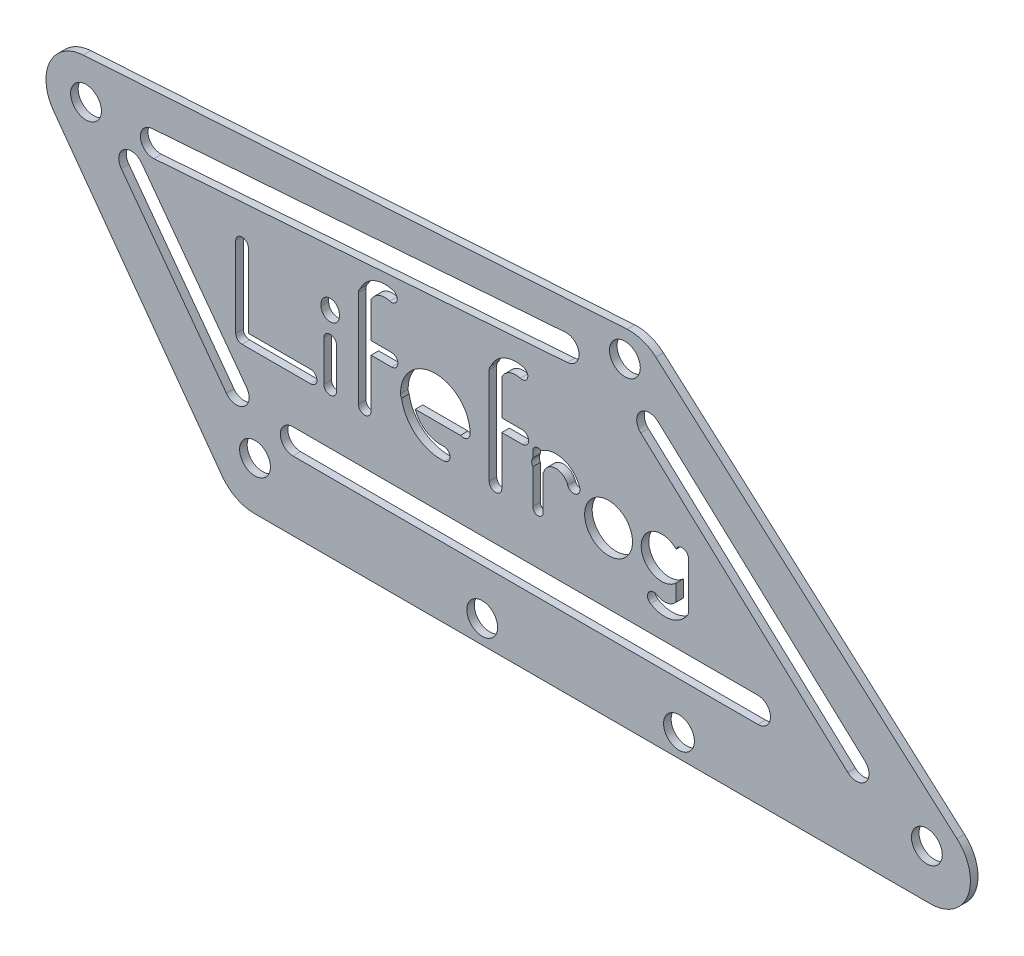
SolidWorks part; units mm, degrees
ref_plane "Front Plane" through (0, 0, 0) normal (0, 0, 1) x (1, 0, 0)
ref_plane "Top Plane" through (0, 0, 0) normal (0, 1, 0) x (1, 0, 0)
ref_plane "Right Plane" through (0, 0, 0) normal (1, 0, 0) x (0, 0, -1)
sketch "Sketch3" plane through (0, 0, 0) normal (0, 0, 1) x (1, 0, 0)
  line L0 (-105.0544, 1.9987) -> (28.8099, 1.9987)
  line L3 (-144.7818, 51.1553) -> (-111.4337, 5.2494)
  line L4 (-130.8953, -6.016) -> (39.056, -6.016)
  line L7 (-138.9015, 63.6585) -> (-31.2776, 70.4842)
  line L8 (-25.5532, 68.52) -> (34.0353, 15.7884)
  arc A0 (28.8099, 1.9987) -> (34.0353, 15.7884) centre (28.8099, 9.8836) ccw
  arc A1 (-25.5532, 68.52) -> (-31.2776, 70.4842) centre (-30.7786, 62.6152) ccw
  arc A2 (-105.0544, 1.9987) -> (-111.4337, 5.2494) centre (-105.0544, 9.8836) cw
  arc A3 (-144.7818, 51.1553) -> (-138.9015, 63.6585) centre (-138.4025, 55.7894) cw
  circle A11 centre (49.307, 58.8735) radius 21
  circle A13 centre (-59.9429, 6.5523) radius 3.05
  circle A14 centre (-104.9148, 11.5444) radius 3.05
  circle A15 centre (-20.9941, 6.4971) radius 3.05
  circle A16 centre (28.0724, 11.5486) radius 3.05
  circle A17 centre (-31.7004, 65.1519) radius 3.05
  circle A18 centre (-138.3619, 55.8478) radius 3.05
  dimension "D1" = 7.8849
  dimension "D2" = 6.1
extrude "Boss-Extrude2" add sketch "Sketch3" along normal blind 1.5 contours A3 L3 A2 L0 A0 L8 A1 L7 A18 A17 A16 A15 A14 A13 region at (-58.2224, 33.7177, 0)
sketch "Sketch4" plane through (0, 0, 1.5) normal (0, 0, 1) x (1, 0, 0)
  line L1 (-26.8632, 55.8937) -> (14.1152, 18.1826) construction
  line L5 (-25.1703, 57.7333) -> (15.8082, 20.0221)
  line L9 (-28.5561, 54.0541) -> (12.4223, 16.343)
  line L13 (-97.4073, 18.1826) -> (-5.3775, 18.1826) construction
  line L23 (-129.3887, 49.4647) -> (-108.5686, 21.3307) construction
  line L26 (-127.3791, 50.9519) -> (-106.559, 22.8178)
  line L29 (-131.3983, 47.9776) -> (-110.5782, 19.8435)
  line L30 (-125.1067, 55.383) -> (-43.278, 61.3603) construction
  line L31 (-125.2888, 57.8764) -> (-43.4601, 63.8537)
  line L32 (-124.9246, 52.8897) -> (-43.0958, 58.867)
  line L33 (-97.4073, 20.6826) -> (-5.3775, 20.6826)
  line L34 (-97.4073, 15.6826) -> (-5.3775, 15.6826)
  line L35 (-107.4816, 46.9298) -> (-107.4816, 31.0422) construction
  line L36 (-106.2316, 46.9298) -> (-106.2316, 31.0422)
  line L37 (-108.7316, 46.9298) -> (-108.7316, 31.0422)
  line L38 (-107.4816, 31.0422) -> (-93.9009, 31.0422) construction
  line L39 (-107.4816, 32.2922) -> (-93.9009, 32.2922)
  line L40 (-107.4816, 29.7922) -> (-93.9009, 29.7922)
  line L41 (-90.0274, 38.986) -> (-90.0274, 31.0422) construction
  line L42 (-88.7774, 38.986) -> (-88.7774, 31.0422)
  line L43 (-91.2774, 38.986) -> (-91.2774, 31.0422)
  line L44 (-90.0274, 44.5942) -> (-90.0274, 44.1452) construction
  line L45 (-88.2261, 44.5942) -> (-88.2261, 44.1452)
  line L46 (-91.8287, 44.5942) -> (-91.8287, 44.1452)
  line L47 (-83.1958, 31.0422) -> (-83.1958, 50.1599) construction
  line L48 (-84.4458, 31.0422) -> (-84.4458, 50.1599)
  line L49 (-81.9458, 31.0422) -> (-81.9458, 50.1599)
  line L50 (-83.1958, 41.9365) -> (-77.886, 41.9365) construction
  line L51 (-83.1958, 43.1865) -> (-77.886, 43.1865)
  line L52 (-83.1958, 40.6865) -> (-77.886, 40.6865)
  line L53 (-74.7394, 37.0381) -> (-63.7024, 37.0381) construction
  line L54 (-74.7394, 38.2881) -> (-63.7024, 38.2881)
  line L55 (-74.7394, 35.7881) -> (-63.7024, 35.7881)
  line L56 (-57.316, 30.7325) -> (-57.316, 49.8502) construction
  line L57 (-58.566, 30.7325) -> (-58.566, 49.8502)
  line L58 (-56.066, 30.7325) -> (-56.066, 49.8502)
  line L59 (-57.316, 41.6268) -> (-52.0062, 41.6268) construction
  line L60 (-57.316, 42.8768) -> (-52.0062, 42.8768)
  line L61 (-57.316, 40.3768) -> (-52.0062, 40.3768)
  line L62 (-48.9003, 30.7325) -> (-48.9003, 40.2914) construction
  line L63 (-49.9346, 30.7325) -> (-49.9346, 40.2914)
  line L64 (-47.8659, 30.7325) -> (-47.8659, 40.2914)
  line L65 (-20.3592, 37.2289) -> (-20.3592, 28.1084) construction
  line L66 (-19.1092, 37.2289) -> (-19.1092, 28.1084)
  line L67 (-21.6092, 37.2289) -> (-21.6092, 28.1084)
  arc A16 (-127.3791, 50.9519) -> (-131.3983, 47.9776) centre (-129.3887, 49.4647) ccw
  arc A17 (-110.5782, 19.8435) -> (-106.559, 22.8178) centre (-108.5686, 21.3307) ccw
  arc A18 (-125.2888, 57.8764) -> (-124.9246, 52.8897) centre (-125.1067, 55.383) ccw
  arc A19 (-43.0958, 58.867) -> (-43.4601, 63.8537) centre (-43.278, 61.3603) ccw
  arc A20 (-25.1703, 57.7333) -> (-28.5561, 54.0541) centre (-26.8632, 55.8937) ccw
  arc A21 (12.4223, 16.343) -> (15.8082, 20.0221) centre (14.1152, 18.1826) ccw
  arc A22 (-97.4073, 20.6826) -> (-97.4073, 15.6826) centre (-97.4073, 18.1826) ccw
  arc A23 (-5.3775, 15.6826) -> (-5.3775, 20.6826) centre (-5.3775, 18.1826) ccw
  arc A24 (-106.2316, 46.9298) -> (-108.7316, 46.9298) centre (-107.4816, 46.9298) ccw
  arc A25 (-108.7316, 31.0422) -> (-106.2316, 31.0422) centre (-107.4816, 31.0422) ccw
  arc A26 (-107.4816, 32.2922) -> (-107.4816, 29.7922) centre (-107.4816, 31.0422) ccw
  arc A27 (-93.9009, 29.7922) -> (-93.9009, 32.2922) centre (-93.9009, 31.0422) ccw
  arc A28 (-88.7774, 38.986) -> (-91.2774, 38.986) centre (-90.0274, 38.986) ccw
  arc A29 (-91.2774, 31.0422) -> (-88.7774, 31.0422) centre (-90.0274, 31.0422) ccw
  arc A30 (-88.2261, 44.5942) -> (-91.8287, 44.5942) centre (-90.0274, 44.5942) ccw
  arc A31 (-91.8287, 44.1452) -> (-88.2261, 44.1452) centre (-90.0274, 44.1452) ccw
  arc A32 (-84.4458, 31.0422) -> (-81.9458, 31.0422) centre (-83.1958, 31.0422) ccw
  arc A33 (-81.9458, 50.1599) -> (-84.4458, 50.1599) centre (-83.1958, 50.1599) ccw
  arc A34 (-83.1958, 50.1599) -> (-77.886, 52.8897) centre (-79.176, 48.8699) cw construction
  arc A35 (-77.5399, 53.9683) -> (-84.2744, 50.5061) centre (-79.176, 48.8699) ccw
  arc A36 (-78.2322, 51.8111) -> (-82.1172, 49.8138) centre (-79.176, 48.8699) ccw
  arc A37 (-78.2322, 51.8111) -> (-77.5399, 53.9683) centre (-77.886, 52.8897) ccw
  arc A38 (-84.2744, 50.5061) -> (-82.1172, 49.8138) centre (-83.1958, 50.1599) ccw
  arc A39 (-83.1958, 43.1865) -> (-83.1958, 40.6865) centre (-83.1958, 41.9365) ccw
  arc A40 (-77.886, 40.6865) -> (-77.886, 43.1865) centre (-77.886, 41.9365) ccw
  arc A41 (-74.7394, 38.2881) -> (-74.7394, 35.7881) centre (-74.7394, 37.0381) ccw
  arc A42 (-63.7024, 35.7881) -> (-63.7024, 38.2881) centre (-63.7024, 37.0381) ccw
  arc A43 (-74.7394, 37.0381) -> (-63.7024, 37.0381) centre (-69.2209, 37.0381) cw construction
  arc A44 (-62.3325, 37.0381) -> (-76.1093, 37.0381) centre (-69.2209, 37.0381) ccw
  arc A45 (-65.0723, 37.0381) -> (-73.3696, 37.0381) centre (-69.2209, 37.0381) ccw
  arc A46 (-65.0723, 37.0381) -> (-62.3325, 37.0381) centre (-63.7024, 37.0381) ccw
  arc A47 (-76.1093, 37.0381) -> (-73.3696, 37.0381) centre (-74.7394, 37.0381) ccw
  arc A48 (-74.7394, 37.0381) -> (-67.5709, 31.0113) centre (-68.1417, 37.609) ccw construction
  arc A49 (-75.9848, 36.9304) -> (-67.4631, 29.766) centre (-68.1417, 37.609) ccw
  arc A50 (-73.4941, 37.1459) -> (-67.6786, 32.2567) centre (-68.1417, 37.609) ccw
  arc A51 (-73.4941, 37.1459) -> (-75.9848, 36.9304) centre (-74.7394, 37.0381) ccw
  arc A52 (-67.4631, 29.766) -> (-67.6786, 32.2567) centre (-67.5709, 31.0113) ccw
  arc A53 (-58.566, 30.7325) -> (-56.066, 30.7325) centre (-57.316, 30.7325) ccw
  arc A54 (-56.066, 49.8502) -> (-58.566, 49.8502) centre (-57.316, 49.8502) ccw
  arc A55 (-57.316, 49.8502) -> (-52.0438, 52.5918) centre (-53.2963, 48.5602) cw construction
  arc A56 (-51.7077, 53.6736) -> (-58.3946, 50.1964) centre (-53.2963, 48.5602) ccw
  arc A57 (-52.3798, 51.5101) -> (-56.2374, 49.5041) centre (-53.2963, 48.5602) ccw
  arc A58 (-52.3798, 51.5101) -> (-51.7077, 53.6736) centre (-52.0438, 52.5918) ccw
  arc A59 (-58.3946, 50.1964) -> (-56.2374, 49.5041) centre (-57.316, 49.8502) ccw
  arc A60 (-57.316, 42.8768) -> (-57.316, 40.3768) centre (-57.316, 41.6268) ccw
  arc A61 (-52.0062, 40.3768) -> (-52.0062, 42.8768) centre (-52.0062, 41.6268) ccw
  arc A62 (-49.9346, 30.7325) -> (-47.8659, 30.7325) centre (-48.9003, 30.7325) ccw
  arc A63 (-47.8659, 40.2914) -> (-49.9346, 40.2914) centre (-48.9003, 40.2914) ccw
  arc A64 (-48.9003, 38.2881) -> (-41.8429, 38.2881) centre (-45.3716, 37.1138) cw construction
  arc A65 (-40.6569, 38.6828) -> (-50.0863, 38.6828) centre (-45.3716, 37.1138) ccw
  arc A66 (-43.029, 37.8934) -> (-47.7142, 37.8934) centre (-45.3716, 37.1138) ccw
  arc A67 (-43.029, 37.8934) -> (-40.6569, 38.6828) centre (-41.8429, 38.2881) ccw
  arc A68 (-50.0863, 38.6828) -> (-47.7142, 37.8934) centre (-48.9003, 38.2881) ccw
  circle A69 centre (-34.9295, 34.565) radius 4.7404
  circle A71 centre (-24.4066, 34.7299) radius 4.0673
  arc A73 (-19.1092, 37.2289) -> (-21.6092, 37.2289) centre (-20.3592, 37.2289) ccw
  arc A74 (-21.6092, 28.1084) -> (-19.1092, 28.1084) centre (-20.3592, 28.1084) ccw
  arc A75 (-20.3592, 28.1084) -> (-25.9689, 26.8183) centre (-23.8091, 30.2683) cw construction
  arc A76 (-26.6322, 25.7588) -> (-19.2997, 27.4451) centre (-23.8091, 30.2683) ccw
  arc A77 (-25.3056, 27.8778) -> (-21.4187, 28.7717) centre (-23.8091, 30.2683) ccw
  arc A78 (-25.3056, 27.8778) -> (-26.6322, 25.7588) centre (-25.9689, 26.8183) ccw
  arc A79 (-19.2997, 27.4451) -> (-21.4187, 28.7717) centre (-20.3592, 28.1084) ccw
  point P3 (-118.9786, 35.3977)
  point P10 (-6.374, 37.0381)
  point P12 (-84.1923, 58.3717)
  point P23 (-51.3924, 18.1826)
  point P30 (-107.4816, 38.986)
  point P35 (-100.6912, 31.0422)
  point P42 (-90.0274, 35.0141)
  point P49 (-90.0274, 44.3697)
  point P56 (-83.1958, 40.6011)
  point P66 (-81.1063, 52.6245)
  point P73 (-80.5409, 41.9365)
  point P78 (-69.2209, 37.0381)
  point P88 (-69.2209, 42.5567)
  point P96 (-72.4033, 32.5401)
  point P101 (-57.316, 40.2914)
  point P111 (-55.244, 52.3058)
  point P118 (-54.6611, 41.6268)
  point P125 (-48.9003, 35.5119)
  point P133 (-45.3716, 40.8327)
  point P146 (-20.3592, 32.6687)
  point P154 (-22.8969, 26.3016)
extrude "Cut-Extrude6" cut sketch "Sketch4" against normal through all both and the other way through all contours A25 L36 A24 L37 | L40 A27 L39 A26 | L43 A28 L42 A29 | L46 A31 L45 A30 | L49 A33 L48 A32 | L52 A40 L51 A39 | A36 A38 A35 A37 | A45 A47 A44 A46 | L55 A42 L54 A41 | A50 A52 A49 A51 | L34 A23 L33 A22 | L57 A54 L58 A53 | L60 A61 L61 A60 | A56 A59 A57 A58 | A66 A68 A65 A67 | A69 | L64 A63 L63 A62 | A71 | L67 A74 L66 A73 | A77 A79 A76 A78 | L9 A21 L5 A20 | L32 A19 L31 A18 | L29 A17 L26 A16
sketch "Sketch5" plane through (0, 0, 1.5) normal (0, 0, 1) x (1, 0, 0)
  line L1 (-73.4557, 41.3578) -> (-64.6349, 41.3578)
  line L2 (-73.4557, 41.3578) -> (-73.4557, 37.3303)
  line L3 (-73.4557, 37.3303) -> (-64.6349, 37.3303)
  line L4 (-64.6349, 41.3578) -> (-64.6349, 37.3303)
extrude "Cut-Extrude7" cut sketch "Sketch5" against normal blind 10
